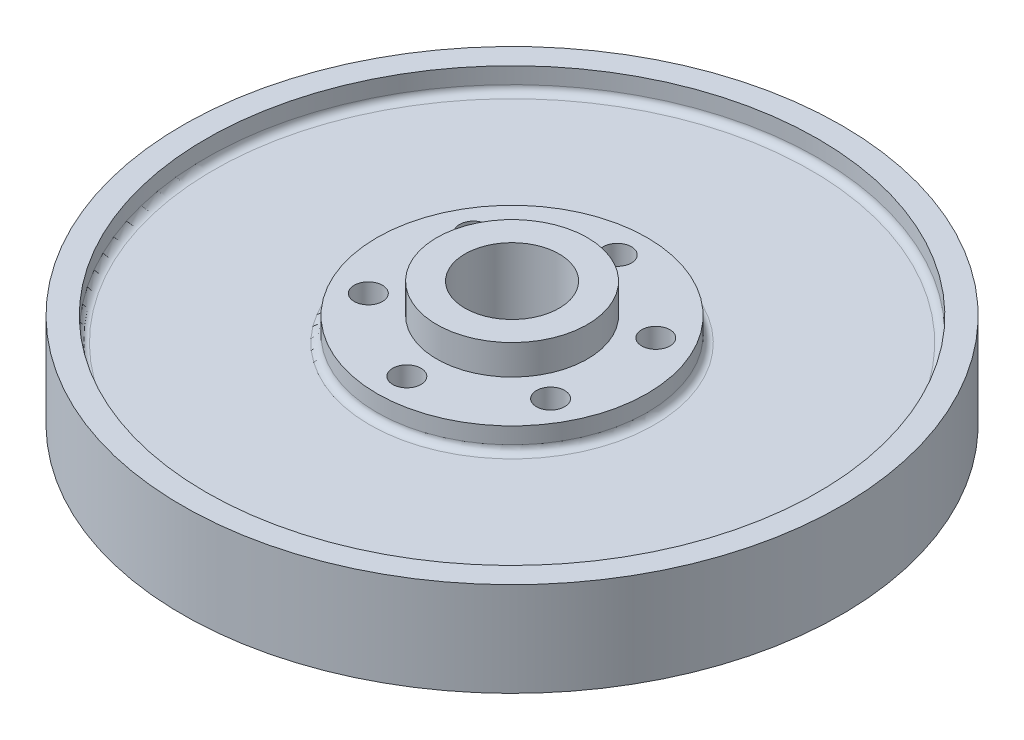
SolidWorks part; units mm, degrees
ref_plane "Front Plane" through (0, 0, 0) normal (0, 0, 1) x (1, 0, 0)
ref_plane "Top Plane" through (0, 0, 0) normal (0, 1, 0) x (1, 0, 0)
ref_plane "Right Plane" through (0, 0, 0) normal (1, 0, 0) x (0, 0, -1)
sketch "Sketch1" plane through (0, 0, 0) normal (0, 0, 1) x (1, 0, 0)
  line L0 (0, 0) -> (0, 10)
  line L3 (32.5, 7.5) -> (32.5, 10)
  line L4 (32.5, 10) -> (35, 10)
  line L5 (35, 10) -> (35, 0)
  line L6 (35, 0) -> (32.5, 0)
  line L7 (32.5, 0) -> (32.5, 2.5)
  line L9 (14.35, 0) -> (0, 0)
  line L10 (0, 5) -> (35, 5) construction
  line L11 (32.5, 7.5) -> (14.35, 7.5)
  line L12 (14.35, 7.5) -> (14.35, 10)
  line L13 (14.35, 0) -> (14.35, 2.5)
  line L14 (14.35, 2.5) -> (32.5, 2.5)
  line L15 (14.35, 10) -> (8, 10)
  line L16 (8, 10) -> (8, 13.175)
  line L17 (8, 13.175) -> (0, 13.175)
  line L18 (0, 13.175) -> (0, 10)
  point P4 (0, 0)
  dimension "D1" = 35
  dimension "D2" = 10
  dimension "D3" = 2.5
  dimension "D4" = 5
  dimension "D6" = 14.35
  dimension "D5" = 10
  dimension "D7" = 3.175
  dimension "D8" = 8
revolve "Main Body" add sketch "Sketch1" angle 360 about L0
fillet "Hub Fillets" radius 0.762 4 edges at (0, 7.5, -14.35) (0, 7.5, -32.5) (0, 2.5, -14.35) (0, 2.5, -32.5)
ref_plane "Blade Drawing Plane" through (35, 0, 0) normal (1, 0, 0) x (0, 0, -1)
sketch "Sketch3" plane through (0, 0, 0) normal (0, -1, 0) x (-1, 0, 0)
  point P0 (0, 11.175)
  dimension "D1" = 11.175
hole_wizard "Ø4.0mm Dowel Hole1" positions "Sketch3" profile "Sketch4" hole size "Ø4.0" standard "ANSI Metric" end condition through all
sketch "Sketch4" plane through (0, 0, -11.175) normal (1, 0, 0) x (0, 0, -1)
  line L0 (0, 0) -> (0, 13.175)
  line L1 (0, 13.175) -> (1.5, 13.175)
  line L2 (1.5, 13.175) -> (1.5, 0)
  line L5 (1.5, 0) -> (0, 0)
  line L11 (0, -6.35) -> (0, 107.95) construction
  dimension "Thru Hole Dia." = 3
  dimension "Thru Hole Depth" = 13.175
pattern_circular "CirPattern1" count 6 over 360 about axis through (0, 0, 0) along (0, -1, 0) of "Ø4.0mm Dowel Hole1"
sketch "Sketch5" plane through (0, 13.175, 0) normal (0, 1, 0) x (1, 0, 0)
  point P0 (0, 0)
hole_wizard "Ø10.0mm Dowel Hole1" positions "Sketch5" profile "Sketch6" hole size "Ø10.0" standard "ANSI Metric" end condition through all
sketch "Sketch6" plane through (0, 13.175, 0) normal (1, 0, 0) x (0, 0, 1)
  line L0 (0, 0) -> (0, 13.175)
  line L1 (0, 13.175) -> (5, 13.175)
  line L2 (5, 13.175) -> (5, 0)
  line L5 (5, 0) -> (0, 0)
  line L11 (0, -6.35) -> (0, 107.95) construction
  dimension "Thru Hole Dia." = 10
  dimension "Thru Hole Depth" = 13.175
equation "\"Shaft_attachment_diam\"= 28.7mm"
equation "\"Thin_section_thickness\"= 5mm"
equation "\"Turbine_annulus_thickness\"= 2.5mm"
equation "\"D4@Sketch1\"=\"Thin_section_thickness\""
equation "\"D6@Sketch1\"=\"Shaft_attachment_diam\"/2"
equation "\"D3@Sketch1\"=\"Turbine_annulus_thickness\""
equation "\"Thick_section_thickness\"= 10mm"
equation "\"Alignment_feature_diam\"= 16mm"
equation "\"Alignment_feature_length\"= 1 / 8"
equation "\"D7@Sketch1\"=\"Alignment_feature_length\""
equation "\"D8@Sketch1\"=\"Alignment_feature_diam\"/2"
equation "\"D5@Sketch1\"=\"Thick_section_thickness\""
